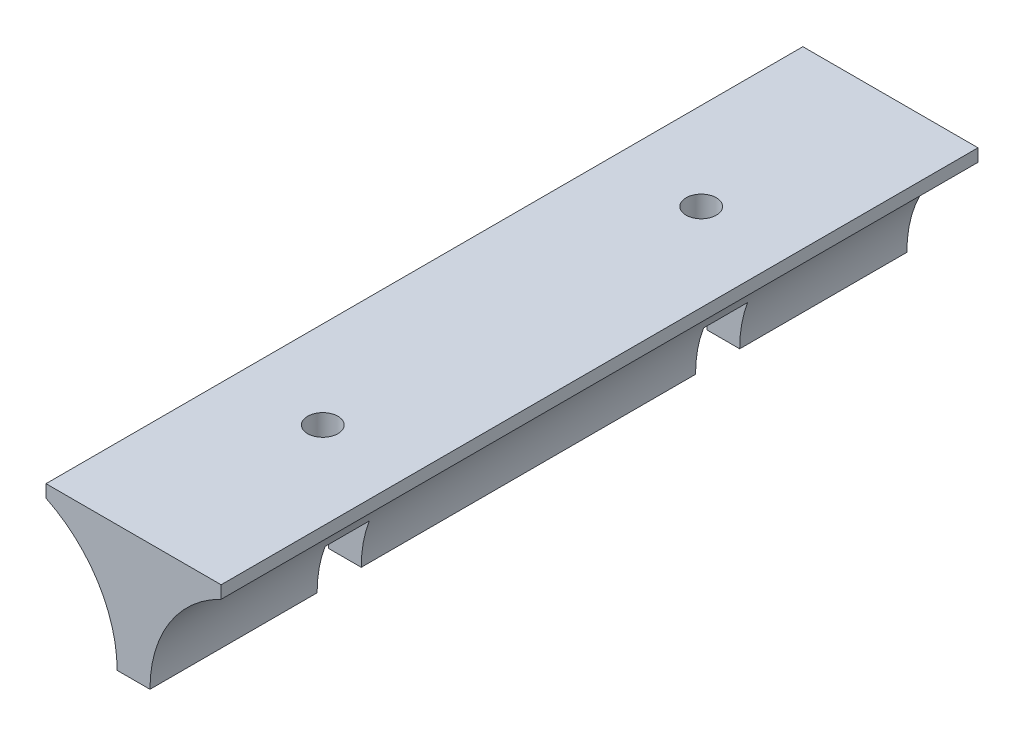
SolidWorks part; units mm, degrees
material "6061-T6 (SS)"
ref_plane "Front" through (0, 0, 0) normal (0, 0, 1) x (1, 0, 0)
ref_plane "Top" through (0, 0, 0) normal (0, 1, 0) x (1, 0, 0)
ref_plane "Right" through (0, 0, 0) normal (1, 0, 0) x (0, 0, -1)
sketch "Sketch1" plane through (0, 0, 0) normal (0, 0, 1) x (1, 0, 0)
  line L0 (-1.3, 0) -> (1.3, 0)
  line L1 (6.9411, 9) -> (6.9411, 10)
  line L2 (6.9411, 10) -> (-6.9411, 10)
  line L3 (-6.9411, 10) -> (-6.9411, 9)
  arc A0 (1.3, 0) -> (6.9411, 9) centre (11.3, 0) cw
  arc A1 (-1.3, 0) -> (-6.9411, 9) centre (-11.3, 0) ccw
  point P9 (0, 0)
  point P10 (0, 10)
  dimension "D1" = 10
  dimension "D2" = 10
  dimension "D3" = 2.6
  dimension "D4" = 1
extrude "Boss-Extrude1" add sketch "Sketch1" along normal mid plane 60
sketch "Sketch2" plane through (0, 10, 0) normal (0, 1, 0) x (1, 0, 0)
  line L0 (0, -30) -> (0, 30) construction
  line L1 (6.9411, -30) -> (-6.9411, -30) construction
  line L2 (6.9411, 30) -> (-6.9411, 30) construction
  point P6 (0, -15)
  point P7 (0, 15)
  dimension "D1" = 15
  dimension "D2" = 15
hole_wizard "Ø2.4 (2.4) Diameter Hole1" positions "3DSketch1" profile "Sketch3" hole size "Ø2.4" standard "ANSI Metric" end condition up to next
sketch3d "3DSketch1"
  point P0 (0, 10, 15)
  point P3 (0, 10, -15)
sketch "Sketch3" plane through (0, 10, 15) normal (1, 0, 0) x (0, 0, 1)
  line L0 (0, 0) -> (0, 10)
  line L1 (0, 10) -> (1.2, 10)
  line L2 (1.2, 10) -> (1.2, 0)
  line L5 (1.2, 0) -> (0, 0)
  line L11 (0, -6.35) -> (0, 107.95) construction
  dimension "Thru Hole Dia." = 2.4
  dimension "Thru Hole Depth" = 10
sketch "Sketch4" plane through (0, 0, 0) normal (0, -1, 0) x (1, 0, 0)
  line L1 (-3.2287, 16.75) -> (3.748, 16.75)
  line L2 (-3.2287, 16.75) -> (-3.2287, 13.25)
  line L3 (-3.2287, 13.25) -> (3.748, 13.25)
  line L4 (3.748, 16.75) -> (3.748, 13.25)
  line L6 (-1.3, 30) -> (1.3, 30) construction
  line L7 (6.9411, 30) -> (6.9411, -30) construction
  line L8 (-4.3792, -13.25) -> (6.9411, -13.25)
  line L9 (-4.3792, -13.25) -> (-4.3792, -16.75)
  line L10 (-4.3792, -16.75) -> (6.9411, -16.75)
  line L11 (6.9411, -13.25) -> (6.9411, -16.75)
  line L12 (-1.3, -30) -> (1.3, -30) construction
  point P6 (-3.2287, 15)
  point P15 (6.9411, -15)
  dimension "D1" = 3.5
  dimension "D2" = 15
  dimension "D3" = 3.5
  dimension "D4" = 15
extrude "Cut-Extrude1" cut sketch "Sketch4" against normal blind 3.5
